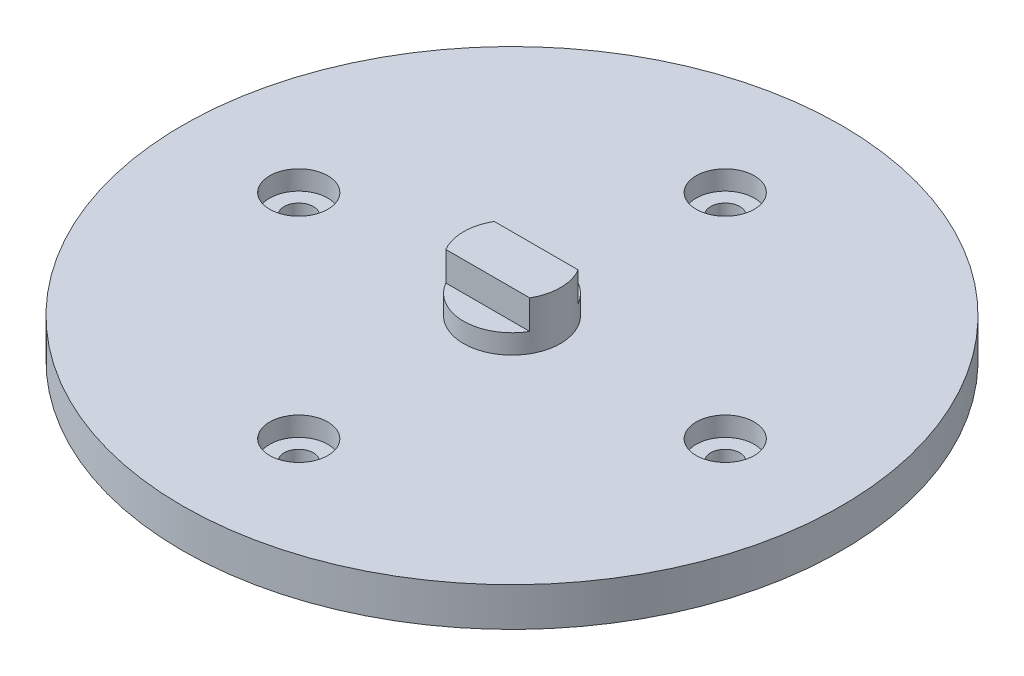
SolidWorks part; units mm, degrees
ref_plane "前视基准面" through (0, 0, 0) normal (0, 0, 1) x (1, 0, 0)
ref_plane "上视基准面" through (0, 0, 0) normal (0, 1, 0) x (1, 0, 0)
ref_plane "右视基准面" through (0, 0, 0) normal (1, 0, 0) x (0, 0, -1)
sketch "草图1" plane through (0, 0, 0) normal (0, 1, 0) x (1, 0, 0)
  circle A0 centre (0, 0) radius 34
  circle A1 centre (0, 0) radius 22 construction
  circle A2 centre (0, 22) radius 1.5
  circle A3 centre (22, 0) radius 1.5
  circle A4 centre (0, -22) radius 1.5
  circle A5 centre (-22, 0) radius 1.5
  circle A6 centre (0, 22) radius 3
  circle A7 centre (22, 0) radius 3
  circle A8 centre (0, -22) radius 3
  circle A9 centre (-22, 0) radius 3
  point P15 (0, 0)
  point P23 (0, 0)
  dimension "D1" = 68
  dimension "D2" = 44
  dimension "D3" = 3
  dimension "D5" = 6
  dimension "D4" = 4
  dimension "D6" = 4
extrude "凸台-拉伸1" add sketch "草图1" along normal blind 4 contours A0 A9 A8 A7 A6 region at (0, 0, 0)
extrude "凸台-拉伸2" add sketch "草图1<3>" along normal blind 2 contours A6 A2 | A7 A3 | A8 A4 | A9 A5 region at (-2.9151, 0, -22) region at (19.0849, 0, 0) region at (-2.9151, 0, 22) region at (-24.9151, 0, 0)
sketch "草图1<3>" plane through (0, 0, 0) normal (0, 1, 0) x (1, 0, 0) same geometry as "草图1"
sketch "草图2" plane through (0, 4, 0) normal (0, 1, 0) x (1, 0, 0)
  circle A0 centre (0, 0) radius 5
  dimension "D1" = 10
extrude "凸台-拉伸3" add sketch "草图2" along normal blind 2
sketch "草图3" plane through (0, 6, 0) normal (0, 1, 0) x (1, 0, 0)
  line L0 (-4.3301, 2.5) -> (4.3301, 2.5)
  line L1 (-5, 0) -> (5, 0) construction
  line L2 (-4.3301, -2.5) -> (4.3301, -2.5)
  circle A0 centre (0, 0) radius 5 construction
  circle A1 centre (0, 0) radius 5 construction
  arc A2 (-4.3301, 2.5) -> (-4.3301, -2.5) centre (0, 0) ccw
  arc A3 (4.3301, -2.5) -> (4.3301, 2.5) centre (0, 0) ccw
  dimension "D1" = 5
extrude "凸台-拉伸4" add sketch "草图3" along normal blind 3
